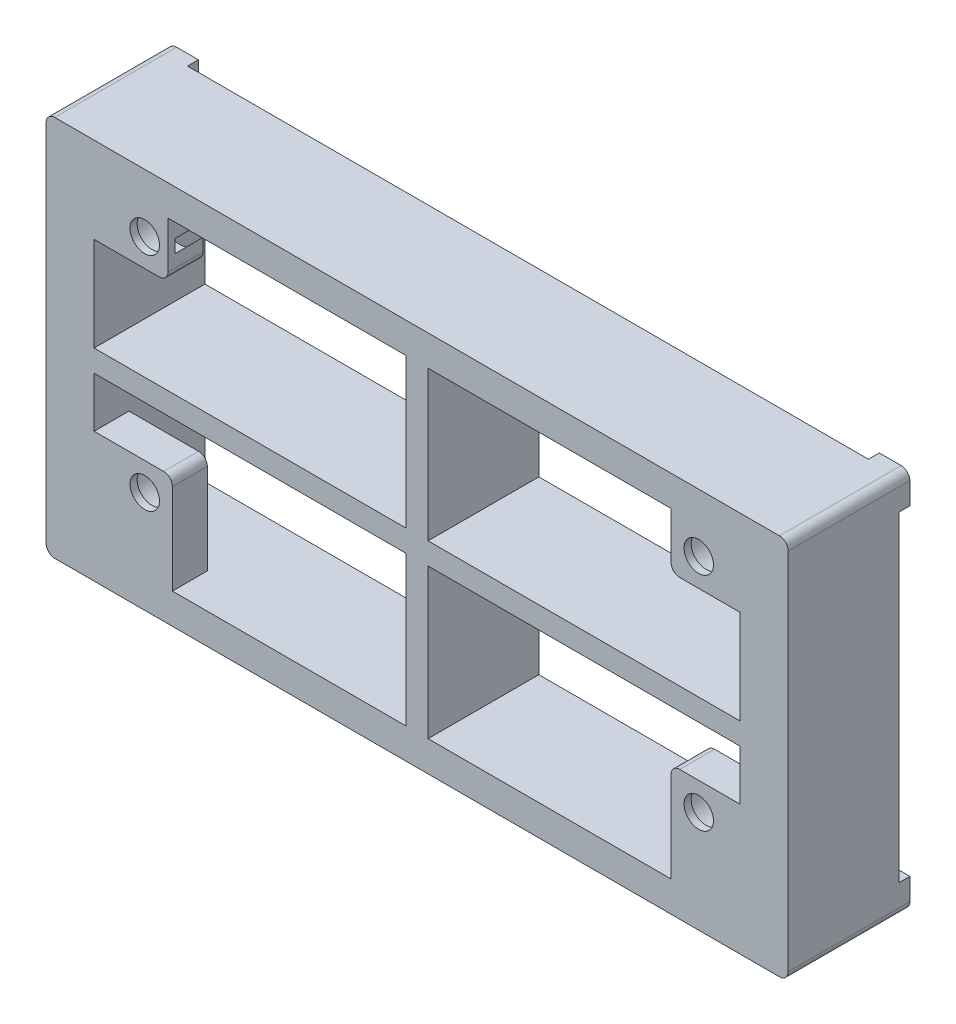
SolidWorks part; units mm, degrees
ref_plane "Front Plane" through (0, 0, 0) normal (0, 0, 1) x (1, 0, 0)
ref_plane "Top Plane" through (0, 0, 0) normal (0, 1, 0) x (1, 0, 0)
ref_plane "Right Plane" through (0, 0, 0) normal (1, 0, 0) x (0, 0, -1)
sketch "Sketch1" plane through (0, 0, 0) normal (0, 0, 1) x (1, 0, 0)
  line L0 (25.2657, -86.1002) -> (25.2657, -168.6502) construction
  line L1 (27.7657, -83.6002) -> (-142.3343, -83.6002)
  line L2 (27.7657, -83.6002) -> (27.7657, -171.1502)
  line L3 (27.7657, -171.1502) -> (-142.3343, -171.1502)
  line L4 (-142.3343, -83.6002) -> (-142.3343, -171.1502)
  line L5 (-139.8343, -168.6502) -> (-139.8343, -86.1002) construction
  line L6 (-139.8343, -86.1002) -> (25.2657, -86.1002) construction
  line L7 (25.2657, -168.6502) -> (-139.8343, -168.6502) construction
  line L9 (-131.3343, -90.6002) -> (16.7657, -90.6002)
  line L10 (-131.3343, -90.6002) -> (-131.3343, -164.1502)
  line L11 (-131.3343, -164.1502) -> (16.7657, -164.1502)
  line L12 (16.7657, -90.6002) -> (16.7657, -164.1502)
  line L13 (-54.7843, -164.1502) -> (-59.7843, -164.1502)
  line L14 (-54.7843, -164.1502) -> (-54.7843, -90.6002)
  line L15 (-54.7843, -90.6002) -> (-59.7843, -90.6002)
  line L16 (-59.7843, -164.1502) -> (-59.7843, -90.6002)
  line L17 (-54.7843, -164.1502) -> (-59.7843, -90.6002) construction
  line L18 (-54.7843, -90.6002) -> (-59.7843, -164.1502) construction
  line L19 (16.7657, -129.8752) -> (-131.3343, -129.8752)
  line L20 (16.7657, -129.8752) -> (16.7657, -124.8752)
  line L21 (16.7657, -124.8752) -> (-131.3343, -124.8752)
  line L22 (-131.3343, -129.8752) -> (-131.3343, -124.8752)
  line L23 (16.7657, -129.8752) -> (-131.3343, -124.8752) construction
  line L24 (16.7657, -124.8752) -> (-131.3343, -129.8752) construction
  point P16 (-57.2843, -127.3752)
  point P22 (-57.2843, -127.3752)
  dimension "D1" = 2.5
  dimension "D2" = 2.5
  dimension "D3" = 2.5
  dimension "D4" = 2.5
  dimension "D5" = 7
  dimension "D6" = 7
  dimension "D7" = 11
  dimension "D8" = 11
  dimension "D9" = 5
  dimension "D10" = 5
extrude "Boss-Extrude1" add sketch "Sketch1" along normal blind 25.4 contours L1 L4 L3 L2 L9 L12 L11 L10 | L16 L21 L10 L19 | L21 L14 L9 L16 | L12 L21 L14 L19 | L14 L19 L16 L11 | L14 L21 L16 L19 region at (25.8526, -127.3752, 0) region at (-57.2843, -107.7377, 0) region at (-95.5593, -127.3752, 0) region at (-57.2843, -127.3752, 0) region at (-19.0093, -127.3752, 0) region at (-57.2843, -147.0127, 0)
sketch "Sketch2" plane through (0, 0, 0) normal (0, 0, -1) x (-1, 0, 0)
  line L0 (-25.2657, -86.1002) -> (-25.2657, -168.6502) construction
  line L1 (-27.7657, -171.1502) -> (-25.2657, -171.1502)
  line L2 (-27.7657, -171.1502) -> (-27.7657, -164.1502)
  line L3 (-27.7657, -164.1502) -> (-25.2657, -164.1502)
  line L4 (-25.2657, -171.1502) -> (-25.2657, -164.1502)
  line L5 (-27.7657, -171.1502) -> (142.3343, -171.1502) construction
  line L6 (-20.7657, -171.1502) -> (-25.2657, -171.1502)
  line L7 (-20.7657, -171.1502) -> (-20.7657, -168.6502)
  line L8 (-20.7657, -168.6502) -> (-25.2657, -168.6502)
  line L9 (-25.2657, -171.1502) -> (-25.2657, -168.6502)
  line L10 (139.8343, -86.1002) -> (-25.2657, -86.1002) construction
  line L11 (-27.7657, -83.6002) -> (-25.2657, -83.6002)
  line L12 (-27.7657, -83.6002) -> (-27.7657, -90.6002)
  line L13 (-27.7657, -90.6002) -> (-25.2657, -90.6002)
  line L14 (-25.2657, -83.6002) -> (-25.2657, -90.6002)
  line L15 (-25.2657, -83.6002) -> (-20.7657, -83.6002)
  line L16 (-25.2657, -83.6002) -> (-25.2657, -86.1002)
  line L17 (-25.2657, -86.1002) -> (-20.7657, -86.1002)
  line L18 (-20.7657, -83.6002) -> (-20.7657, -86.1002)
  line L19 (142.3343, -83.6002) -> (142.3343, -171.1502) construction
  line L20 (135.3343, -171.1502) -> (142.3343, -171.1502)
  line L21 (135.3343, -171.1502) -> (135.3343, -168.6502)
  line L22 (135.3343, -168.6502) -> (142.3343, -168.6502)
  line L23 (142.3343, -171.1502) -> (142.3343, -168.6502)
  line L24 (139.8343, -168.6502) -> (139.8343, -86.1002) construction
  line L25 (139.8343, -164.1502) -> (142.3343, -164.1502)
  line L26 (139.8343, -164.1502) -> (139.8343, -168.6502)
  line L27 (139.8343, -168.6502) -> (142.3343, -168.6502)
  line L28 (142.3343, -164.1502) -> (142.3343, -168.6502)
  line L29 (-27.7657, -83.6002) -> (142.3343, -83.6002) construction
  line L30 (139.8343, -90.6002) -> (142.3343, -90.6002)
  line L31 (139.8343, -90.6002) -> (139.8343, -83.6002)
  line L32 (139.8343, -83.6002) -> (142.3343, -83.6002)
  line L33 (142.3343, -90.6002) -> (142.3343, -83.6002)
  line L34 (139.8343, -86.1002) -> (135.3328, -86.1002)
  line L35 (139.8343, -86.1002) -> (139.8343, -83.6002)
  line L36 (139.8343, -83.6002) -> (135.3328, -83.6002)
  line L37 (135.3328, -86.1002) -> (135.3328, -83.6002)
  line M19 (142.3343, -83.6002) -> (-27.7657, -83.6002)
  line M20 (-27.7657, -83.6002) -> (-27.7657, -171.1502)
  line M21 (-27.7657, -171.1502) -> (142.3343, -171.1502)
  line M22 (142.3343, -171.1502) -> (142.3343, -83.6002)
  dimension "D1" = 7
  dimension "D2" = 7
  dimension "D3" = 7
  dimension "D4" = 7
  dimension "D5" = 7
extrude "Boss-Extrude2" add sketch "Sketch2" along normal blind 2.5 contours L22 L21 M21 M22 | L25 L26 L22 M22 | L31 L30 M22 M19 | L37 L34 L31 M19 | L14 L13 M19 M20 | L18 L14 L17 M19 | L4 L3 M21 M20 | L9 L8 L7 L6 region at (26.5157, -167.6502, 0) region at (26.5157, -87.1002, 0) region at (-138.8343, -169.9002, 0) region at (23.0157, -84.8502, 0) region at (-141.0843, -166.4002, 0) region at (-137.5836, -84.8502, 0) region at (-141.0843, -87.1002, 0)
sketch "Sketch3" plane through (0, 0, 0) normal (0, 0, -1) x (-1, 0, 0)
  circle A0 centre (-20.2657, -163.6502) radius 1.5
  circle A1 centre (-20.2657, -91.1002) radius 1.5
  circle A2 centre (134.8343, -163.6502) radius 1.5
  dimension "D1" = 3
  dimension "D2" = 3
  dimension "D3" = 3
extrude "Boss-Extrude3" add sketch "Sketch3" along normal blind 1
sketch "Sketch4" plane through (0, 0, 25.4) normal (0, 0, 1) x (1, 0, 0)
  line L0 (16.7657, -90.6002) -> (16.7657, -124.8752) construction
  line L3 (-54.7843, -90.6002) -> (16.7657, -90.6002) construction
  line L5 (16.7657, -129.8752) -> (16.7657, -164.1502) construction
  line L6 (16.7657, -90.6002) -> (0.9157, -90.6002)
  line L7 (16.7657, -90.6002) -> (16.7657, -103.3002)
  line L8 (16.7657, -103.3002) -> (2.9157, -103.3002)
  line L9 (0.9157, -90.6002) -> (0.9157, -101.3002)
  line L10 (-131.3343, -164.1502) -> (-113.3843, -164.1502)
  line L11 (-131.3343, -164.1502) -> (-131.3343, -141.4002)
  line L12 (-131.3343, -141.4002) -> (-115.3843, -141.4002)
  line L13 (-113.3843, -164.1502) -> (-113.3843, -143.4002)
  line L14 (-131.3343, -90.6002) -> (-114.3843, -90.6002)
  line L15 (-131.3343, -90.6002) -> (-131.3343, -103.3002)
  line L16 (-131.3343, -103.3002) -> (-116.3843, -103.3002)
  line L17 (-114.3843, -90.6002) -> (-114.3843, -101.3002)
  line L18 (16.7657, -141.4002) -> (2.9157, -141.4002)
  line L19 (16.7657, -141.4002) -> (16.7657, -164.1502)
  line L20 (16.7657, -164.1502) -> (0.9157, -164.1502)
  line L21 (0.9157, -143.4002) -> (0.9157, -164.1502)
  line L22 (-54.7843, -164.1502) -> (16.7657, -164.1502) construction
  arc A0 (-116.3843, -103.3002) -> (-114.3843, -101.3002) centre (-116.3843, -101.3002) ccw
  arc A1 (-115.3843, -141.4002) -> (-113.3843, -143.4002) centre (-115.3843, -143.4002) cw
  arc A2 (0.9157, -143.4002) -> (2.9157, -141.4002) centre (2.9157, -143.4002) cw
  arc A3 (0.9157, -101.3002) -> (2.9157, -103.3002) centre (2.9157, -101.3002) ccw
  point P0 (7.2657, -147.7502)
  point P1 (7.2657, -96.9502)
  point P2 (-119.7343, -96.9502)
  point P3 (-119.7343, -147.7502)
  point P39 (7.2657, -147.7502)
  point P40 (7.2657, -96.9502)
  point P41 (7.2657, -96.9502)
  point P42 (0, 0)
  point P43 (0, 0)
  dimension "D9" = 2
  dimension "D1" = 50.8
  dimension "D2" = 127
  dimension "D3" = 9.5
  dimension "D4" = 6.35
  dimension "D5" = 6.35
  dimension "D6" = 6.35
  dimension "D7" = 6.35
  dimension "D8" = 0
  dimension "D10" = 50.8
  dimension "D11" = 0
  dimension "D12" = 0
  dimension "D13" = 6.35
  dimension "D14" = 6.35
extrude "Boss-Extrude4" add sketch "Sketch4" against normal blind 8
hole_wizard "CBORE for 1/4 Socket Head Cap Screw1" positions "Sketch10" profile "Sketch11" counterbore size "1/4" standard "ANSI Inch" end condition through all
sketch "Sketch10" plane through (0, 0, 17.4) normal (0, 0, -1) x (-1, 0, 0)
  point P0 (-7.2657, -147.7502)
  point P3 (-7.2657, -96.9502)
  point P6 (119.7343, -96.9502)
  point P9 (119.7343, -147.7502)
sketch "Sketch11" plane through (7.2657, -147.7502, 17.4) normal (1, 0, 0) x (0, 1, 0)
  line L0 (0, 0) -> (0, 8)
  line L1 (0, 8) -> (3.3782, 8)
  line L3 (3.3782, 8) -> (3.3782, 6.35)
  line L4 (3.3782, 6.35) -> (5.5562, 6.35)
  line L5 (5.5562, 6.35) -> (5.5562, 0)
  line L7 (5.5562, 0) -> (0, 0)
  line L11 (0, -6.35) -> (0, 107.95) construction
  dimension "Thru Hole Dia." = 6.7564
  dimension "Thru Hole Depth" = 8
  dimension "C'Bore Dia." = 11.1125
  dimension "C'Bore Depth" = 6.35
fillet "Fillet1" radius 1 3 edges at (-136.3343, -163.6502, -1) (18.7657, -91.1002, -1) (18.7657, -163.6502, -1)
fillet "Fillet2" radius 2 4 edges at (-142.3343, -83.6002, 11.45) (-142.3343, -171.1502, 11.45) (27.7657, -83.6002, 11.45) (27.7657, -171.1502, 11.45)
